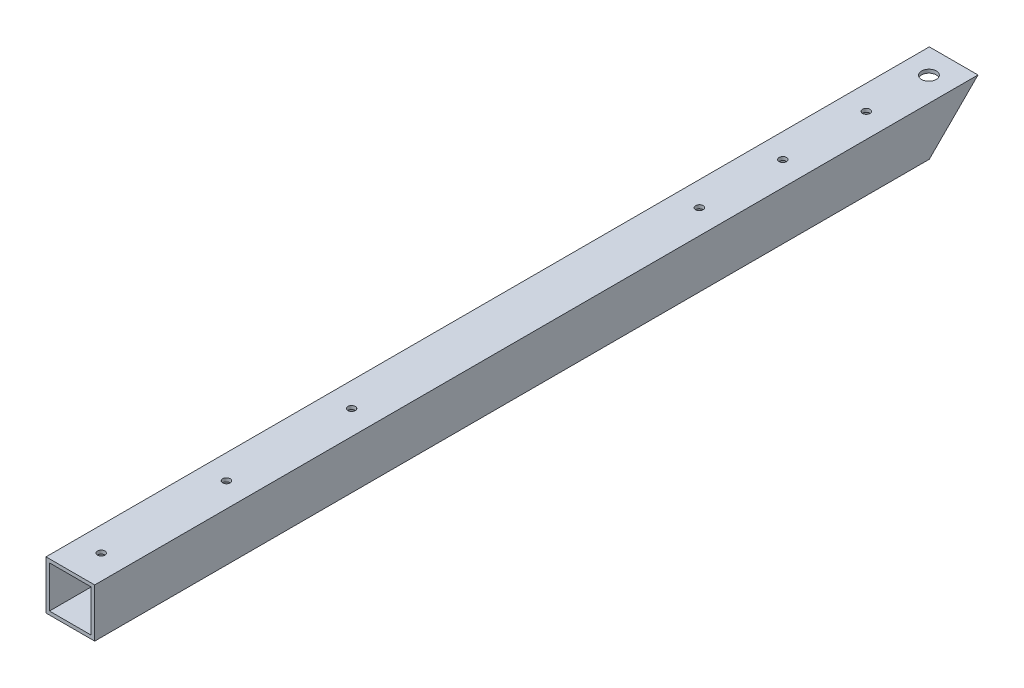
SolidWorks part; units mm, degrees
material "6061 Alloy"
ref_plane "Front Plane" through (0, 0, 0) normal (0, 0, 1) x (1, 0, 0)
ref_plane "Top Plane" through (0, 0, 0) normal (0, 1, 0) x (1, 0, 0)
ref_plane "Right Plane" through (0, 0, 0) normal (1, 0, 0) x (0, 0, -1)
sketch "Sketch1" plane through (0, 0, 0) normal (0, 0, 1) x (1, 0, 0)
  line L1 (-22.225, -22.225) -> (22.225, -22.225)
  line L2 (-22.225, -22.225) -> (-22.225, 22.225)
  line L3 (-22.225, 22.225) -> (22.225, 22.225)
  line L4 (22.225, -22.225) -> (22.225, 22.225)
  line L5 (-22.225, -22.225) -> (22.225, 22.225) construction
  line L6 (-22.225, 22.225) -> (22.225, -22.225) construction
  line L7 (-19.05, -19.05) -> (19.05, -19.05)
  line L8 (-19.05, -19.05) -> (-19.05, 19.05)
  line L9 (-19.05, 19.05) -> (19.05, 19.05)
  line L10 (19.05, -19.05) -> (19.05, 19.05)
  line L11 (-19.05, -19.05) -> (19.05, 19.05) construction
  line L12 (-19.05, 19.05) -> (19.05, -19.05) construction
  point P0 (0, 0)
  point P6 (0, 0)
  dimension "D1" = 44.45
  dimension "D2" = 3.175
extrude "Boss-Extrude1" add sketch "Sketch1" along normal blind 1044.575
hole_wizard "1/4 Clearance Hole3" positions "Sketch8" profile "Sketch9" hole size "1/4" standard "ANSI Inch" end condition through all
sketch "Sketch8" plane through (0, 22.225, 0) normal (0, 1, 0) x (1, 0, 0)
  line L0 (0, 0) -> (0, -1044.575) construction
  line L1 (22.225, 0) -> (-22.225, 0) construction
  line L2 (22.225, -1044.575) -> (-22.225, -1044.575) construction
  line L5 (-22.225, -260.985) -> (0, -260.985) construction
  line L6 (-22.225, -1044.575) -> (-22.225, 0) construction
  point P0 (0, -318.135)
  point P2 (0, -394.335)
  point P4 (0, -470.535)
  point P26 (0, -788.035)
  point P29 (0, -902.335)
  point P31 (0, -1016.635)
  dimension "D1" = 57.15
  dimension "D2" = 76.2
  dimension "D3" = 76.2
  dimension "D4" = 260.985
  dimension "D5" = 527.05
  dimension "D6" = 114.3
  dimension "D7" = 114.3
sketch "Sketch9" plane through (0, 22.225, 318.135) normal (1, 0, 0) x (0, 0, 1)
  line L0 (0, 0) -> (0, 44.45)
  line L1 (0, 44.45) -> (3.3782, 44.45)
  line L2 (3.3782, 44.45) -> (3.3782, 0)
  line L5 (3.3782, 0) -> (0, 0)
  line L11 (0, -6.35) -> (0, 107.95) construction
  dimension "Thru Hole Dia." = 6.7564
  dimension "Thru Hole Depth" = 44.45
hole_wizard "1/2 Clearance Hole1" positions "Sketch10" profile "Sketch11" hole size "1/2" standard "ANSI Inch" end condition through all
sketch "Sketch10" [suppressed] plane through (0, 22.225, 0) normal (0, 1, 0) x (1, 0, 0)
  point P0 (0, -260.985)
sketch "Sketch11" plane through (0, 22.225, 260.985) normal (1, 0, 0) x (0, 0, 1)
  line L0 (0, 0) -> (0, 44.45)
  line L1 (0, 44.45) -> (6.7462, 44.45)
  line L2 (6.7462, 44.45) -> (6.7462, 0)
  line L5 (6.7462, 0) -> (0, 0)
  line L11 (0, -6.35) -> (0, 107.95) construction
  dimension "Thru Hole Dia." = 13.4925
  dimension "Thru Hole Depth" = 44.45
sketch "Sketch17" plane through (-22.225, 0, 0) normal (-1, 0, 0) x (0, 0, 1)
  line L0 (267.7312, 22.225) -> (254.2388, 22.225) construction
  line L1 (267.7312, 22.225) -> (254.2388, 22.225) construction
  line L2 (254.2388, 19.05) -> (267.7312, 19.05) construction
  line L3 (254.2388, 19.05) -> (267.7312, 19.05) construction
  line L4 (282.8138, -22.225) -> (238.3638, 22.225)
  line L5 (1044.575, -22.225) -> (0, -22.225) construction
  line L6 (1044.575, 22.225) -> (0, 22.225) construction
  line L7 (314.7568, -22.225) -> (321.5132, -22.225) construction
  line L8 (314.7568, -22.225) -> (321.5132, -22.225) construction
  line L9 (254.2388, 19.05) -> (241.5388, 19.05) construction
  line L10 (282.8138, -22.225) -> (0, -22.225)
  line L11 (0, -22.225) -> (0, 22.225)
  line L12 (0, 22.225) -> (238.3638, 22.225)
  dimension "D1" = 45
  dimension "D2" = 12.7
extrude "Cut-Extrude1" cut sketch "Sketch17" against normal through all
sketch "Sketch19" plane through (22.225, 0, 0) normal (1, 0, 0) x (0, 0, -1)
  line L0 (-238.3638, 22.225) -> (-1044.8138, 22.225)
  dimension "D1" = 806.45
ref_plane "Plane1" through (0, 0, 1044.8138) normal (0, 0, 1) x (1, 0, 0)
sketch "Sketch18" plane through (0, 0, 1044.575) normal (0, 0, 1) x (1, 0, 0)
  line L0 (-22.225, 22.225) -> (-22.225, -22.225) construction
  line L1 (-19.05, 19.05) -> (-19.05, -19.05) construction
  line L2 (22.225, 22.225) -> (-22.225, 22.225) construction
  line L3 (19.05, 19.05) -> (-19.05, 19.05) construction
  line L4 (22.225, -22.225) -> (22.225, 22.225) construction
  line L5 (19.05, -19.05) -> (19.05, 19.05) construction
  line L6 (-19.05, -19.05) -> (19.05, -19.05) construction
  line L7 (-22.225, -22.225) -> (22.225, -22.225) construction
  line L8 (-22.225, 22.225) -> (-22.225, -22.225)
  line L9 (-19.05, 19.05) -> (-19.05, -19.05)
  line L10 (22.225, 22.225) -> (-22.225, 22.225)
  line L11 (19.05, 19.05) -> (-19.05, 19.05)
  line L12 (22.225, -22.225) -> (22.225, 22.225)
  line L13 (19.05, -19.05) -> (19.05, 19.05)
  line L14 (-19.05, -19.05) -> (19.05, -19.05)
  line L15 (-22.225, -22.225) -> (22.225, -22.225)
extrude "Boss-Extrude2" add sketch "Sketch18" along normal up to surface (0.2388 mm away) up to plane "Plane1"
